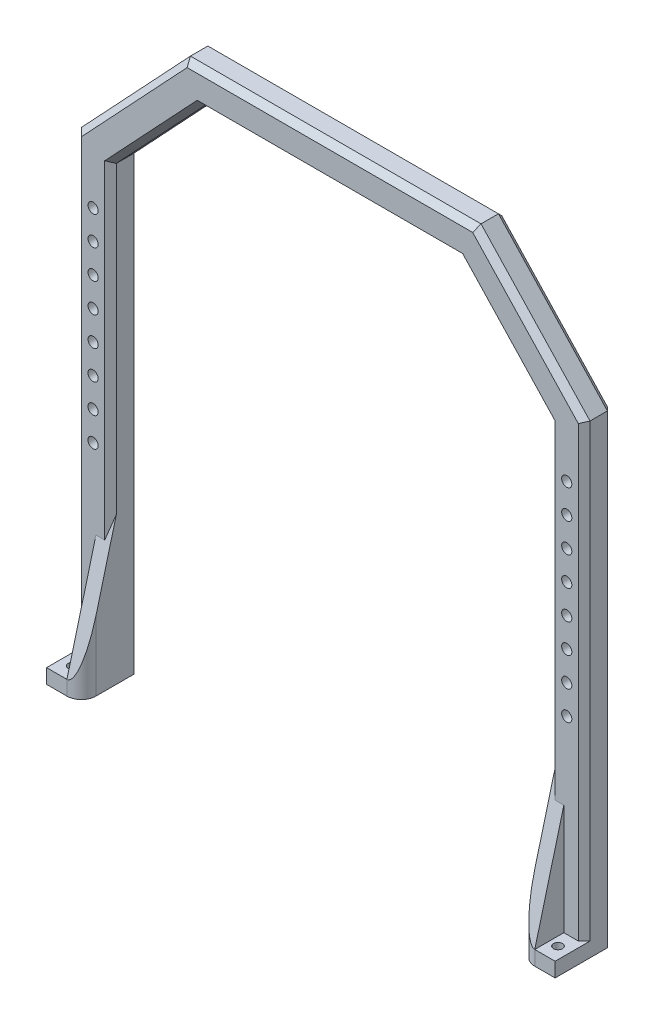
SolidWorks part; units mm, degrees
ref_plane "Front Plane" through (0, 0, 0) normal (0, 0, 1) x (1, 0, 0)
ref_plane "Top Plane" through (0, 0, 0) normal (0, 1, 0) x (1, 0, 0)
ref_plane "Right Plane" through (0, 0, 0) normal (1, 0, 0) x (0, 0, -1)
sketch "Sketch1" plane through (0, 0, 0) normal (0, 0, 1) x (1, 0, 0)
  line L0 (-87.5, -200) -> (-87.5, -40)
  line L1 (-87.5, -40) -> (-50, 0)
  line L2 (-50, 0) -> (50, 0)
  line L3 (50, 0) -> (87.5, -40)
  line L4 (87.5, -40) -> (87.5, -200)
  line L5 (-87.5, -40) -> (87.5, -40) construction
  line L6 (0, -40) -> (0, 0) construction
  line L7 (-87.5, -200) -> (87.5, -200) construction
  line L8 (-75.5, -200) -> (-75.5, -44.7454)
  line L9 (-75.5, -44.7454) -> (-44.8012, -12)
  line L10 (-44.8012, -12) -> (44.8012, -12)
  line L11 (44.8012, -12) -> (75.5, -44.7454)
  line L12 (75.5, -44.7454) -> (75.5, -200)
  line L13 (-87.5, -200) -> (-75.5, -200)
  line L14 (75.5, -200) -> (87.5, -200)
  dimension "D1" = 100
  dimension "D2" = 175
  dimension "D3" = 40
  dimension "D4" = 160
  dimension "D5" = 12
extrude "Boss-Extrude1" add sketch "Sketch1" along normal blind 5 and the other way blind 5
sketch "Sketch2" plane through (0, 0, 5) normal (0, 0, 1) x (1, 0, 0)
  line L0 (-75.5, -200) -> (-75.5, -44.7454) construction
  line L1 (-87.5, -200) -> (-75.5, -200)
  line L2 (-87.5, -200) -> (-87.5, -195)
  line L3 (-87.5, -195) -> (-80.5, -195)
  line L4 (-75.5, -200) -> (-75.5, -197)
  line L5 (-87.5, -40) -> (-87.5, -200) construction
  line L7 (-80.5, -195) -> (-80.5, -157)
  line L8 (-80.5, -157) -> (-75.5, -157)
  line L9 (-75.5, -197) -> (-75.5, -157)
  dimension "D1" = 5
  dimension "D2" = 40
  dimension "D3" = 7
extrude "Boss-Extrude2" add sketch "Sketch2" along normal blind 10
sketch "Sketch3" plane through (-80.5, 0, 0) normal (-1, 0, 0) x (0, 0, 1)
  line L0 (5, -157) -> (15, -195)
  line L1 (15, -195) -> (15, -157)
  line L2 (15, -157) -> (5, -157)
extrude "Cut-Extrude1" cut sketch "Sketch3" against normal through all
sketch "Sketch4" plane through (0, -195, 0) normal (0, 1, 0) x (1, 0, 0)
  line L0 (-87.5, -15) -> (-87.5, -5) construction
  line L1 (-80.5, -15) -> (-87.5, -15) construction
  circle A0 centre (-83.5, -10) radius 1.5537
  dimension "D1" = 4
  dimension "D2" = 5
extrude "Cut-Extrude2" cut sketch "Sketch4" against normal through all
mirror "Mirror1" about plane through (0, 0, 0) normal (1, 0, 0) of "Cut-Extrude1", "Boss-Extrude2", "Cut-Extrude2"
chamfer "Chamfer1" distance 2 angle 45 12 edges at (-75.5, -122.3727, -5) (-60.1506, -28.3727, -5) (0, -12, -5) (60.1506, -28.3727, -5) (75.5, -122.3727, -5) (81.5, -200, -5) (87.5, -120, -5) (68.75, -20, -5) (0, 0, -5) (-68.75, -20, -5) (-87.5, -120, -5) (-81.5, -200, -5)
chamfer "Chamfer2" distance 2 angle 45 10 edges at (75.5, -100.8727, 5) (60.1506, -28.3727, 5) (0, -12, 5) (-75.5, -100.8727, 5) (-60.1506, -28.3727, 5) (87.5, -117.5, 5) (68.75, -20, 5) (0, 0, 5) (-68.75, -20, 5) (-87.5, -117.5, 5)
fillet "Fillet1" radius 5 2 edges at (75.5, -197.5, 15) (-75.5, -197.5, 15)
sketch "Sketch5" plane through (0, 0, -5) normal (0, 0, -1) x (-1, 0, 0)
  line L0 (-85.5, -130) -> (-77.5, -130) construction
  line L1 (-85.5, -40.7909) -> (-85.5, -198) construction
  line L2 (-77.5, -198) -> (-77.5, -43.9545) construction
  line L3 (-75.5, -200) -> (-87.5, -200) construction
  line L5 (0, 11) -> (0, -11) construction
  circle A0 centre (-81.5, -130) radius 1.75
  circle A1 centre (81.5, -130) radius 1.75
  dimension "D2" = 3.5
  dimension "D1" = 70
extrude "Cut-Extrude3" cut sketch "Sketch5" against normal through all
pattern_linear "LPattern1" count 8 spacing 10 along (0, 1, 0) of "Cut-Extrude3"
